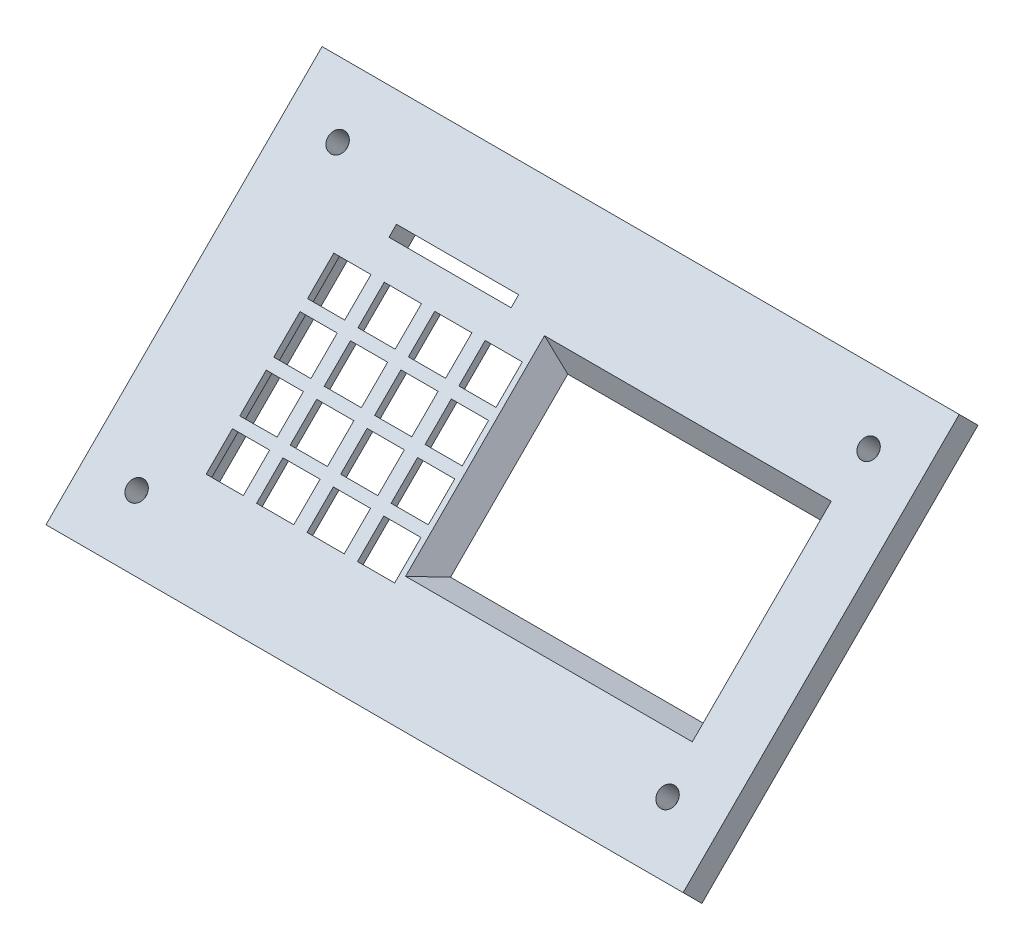
SolidWorks part; units mm, degrees
ref_plane "Спереди" through (0, 0, 0) normal (0, 0, 1) x (1, 0, 0)
ref_plane "Сверху" through (0, 0, 0) normal (0, 1, 0) x (1, 0, 0)
ref_plane "Справа" through (0, 0, 0) normal (1, 0, 0) x (0, 0, -1)
ref_plane "Плоскость4" through (0, 0, 0) normal (0, 0.7071, 0.7071) x (1, 0, 0)
sketch "Эскиз1" plane through (0, 0, 0) normal (0, 0.7071, 0.7071) x (1, 0, 0)
  line L0 (58, 52) -> (106, 52)
  line L1 (120, 0) -> (120, 73.5391)
  line L2 (106, 52) -> (106, 21)
  line L3 (106, 21) -> (58, 21)
  line L4 (58, 21) -> (58, 52)
  line L5 (48, 58) -> (48, 56)
  line L6 (120, -28.6) -> (120, 28.6) construction
  line L7 (120, 73.5391) -> (0, 73.5391) construction
  line L8 (0, 73.5391) -> (0, 0)
  line L9 (48, 58) -> (25, 58)
  line L10 (25, 58) -> (25, 56)
  line L11 (0, 28.6) -> (0, -28.6) construction
  line L12 (0, 0) -> (120, 0)
  line L13 (0, 73.5391) -> (120, 73.5391)
  line L14 (54, 50.5) -> (47, 50.5)
  line L15 (25, 56) -> (48, 56)
  line L16 (44.5, 50.5) -> (37.5, 50.5)
  line L18 (35, 50.5) -> (28, 50.5)
  line L20 (25.5, 50.5) -> (18.5, 50.5)
  line L21 (18.5, 50.5) -> (18.5, 43.5)
  line L22 (18.5, 43.5) -> (25.5, 43.5)
  line L23 (25.5, 43.5) -> (25.5, 50.5)
  line L24 (18.5, 41.5) -> (25.5, 41.5)
  line L25 (25.5, 41.5) -> (25.5, 34.5)
  line L26 (25.5, 34.5) -> (18.5, 34.5)
  line L27 (18.5, 34.5) -> (18.5, 41.5)
  line L28 (18.5, 32.5) -> (18.5, 25.4558)
  line L29 (0, 25.4558) -> (120, 25.4558) construction
  line L30 (18.5, 25.4558) -> (25.5, 25.5)
  line L31 (25.5, 25.5) -> (25.5, 32.5)
  line L32 (25.5, 32.5) -> (18.5, 32.5)
  line L33 (18.5, 23.5) -> (18.5, 16.5)
  line L34 (18.5, 16.5) -> (25.5, 16.5)
  line L35 (25.5, 16.5) -> (25.5, 23.5)
  line L36 (25.5, 23.5) -> (18.5, 23.5)
  line L37 (28, 16.5) -> (28, 23.5)
  line L38 (28, 23.5) -> (35, 23.5)
  line L39 (35, 23.5) -> (35, 16.5)
  line L40 (35, 16.5) -> (28, 16.5)
  line L41 (37.5, 23.5) -> (37.5, 16.5)
  line L42 (37.5, 16.5) -> (44.5, 16.5)
  line L43 (44.5, 16.5) -> (44.5, 23.5)
  line L44 (44.5, 23.5) -> (37.5, 23.5)
  line L45 (47, 16.5) -> (47, 23.5)
  line L46 (47, 23.5) -> (54, 23.5)
  line L47 (54, 23.5) -> (54, 16.5)
  line L48 (54, 16.5) -> (47, 16.5)
  line L49 (54, 25.4558) -> (54, 32.5)
  line L50 (54, 32.5) -> (47, 32.5)
  line L51 (47, 32.5) -> (47, 25.4558)
  line L52 (47, 25.4558) -> (54, 25.4558)
  line L53 (44.5, 34.5) -> (44.5, 41.5)
  line L54 (44.5, 41.5) -> (37.5, 41.5)
  line L55 (37.5, 41.5) -> (37.5, 34.5)
  line L56 (37.5, 34.5) -> (44.5, 34.5)
  line L57 (35, 43.5) -> (28, 43.5)
  line L58 (28, 43.5) -> (28, 50.5)
  line L59 (35, 43.5) -> (35, 50.5)
  line L60 (37.5, 43.5) -> (37.5, 50.5)
  line L61 (44.5, 50.5) -> (44.5, 43.5)
  line L62 (44.5, 43.5) -> (37.5, 43.5)
  line L63 (54, 50.5) -> (54, 43.5)
  line L64 (47, 43.5) -> (47, 50.5)
  line L65 (54, 43.5) -> (47, 43.5)
  line L66 (47, 41.5) -> (47, 34.5)
  line L67 (47, 34.5) -> (54, 34.5)
  line L68 (54, 34.5) -> (54, 41.5)
  line L69 (54, 41.5) -> (47, 41.5)
  line L70 (28, 41.5) -> (35, 41.5)
  line L71 (35, 41.5) -> (35, 34.5)
  line L72 (35, 34.5) -> (28, 34.5)
  line L73 (28, 34.5) -> (28, 41.5)
  line L74 (28, 32.5) -> (28, 25.4558)
  line L75 (28, 25.4558) -> (35, 25.4558)
  line L76 (35, 25.4558) -> (35, 32.5)
  line L77 (35, 32.5) -> (28, 32.5)
  line L78 (37.5, 32.5) -> (37.5, 25.4558)
  line L79 (37.5, 25.4558) -> (44.5, 25.4558)
  line L80 (44.5, 25.4558) -> (44.5, 32.5)
  line L81 (44.5, 32.5) -> (37.5, 32.5)
  circle A0 centre (10, 63.5391) radius 1.8
  circle A1 centre (110, 63.5391) radius 1.8
  circle A2 centre (110, 10) radius 1.8
  circle A3 centre (10, 10) radius 1.8
extrude "Бобышка-Вытянуть1" add sketch "Эскиз1" along normal blind 5
chamfer "Фаска1" distance 3 angle 60 4 edges at (58, 29.3449, -22.2739) (82, 18.3848, -11.3137) (106, 29.3449, -22.2739) (82, 40.3051, -33.234) first distance on face at (110, 9.3338, -2.2627)
sketch "Эскиз2" plane through (0, 0, 0) normal (0, 0.7071, 0.7071) x (1, 0, 0)
  line L0 (17.5, 15.5428) -> (17.5, 51.6529)
  line L1 (17.5, 51.6529) -> (55, 51.6529)
  line L4 (17.5, 15.5428) -> (55, 15.5428)
  line L5 (55, 15) -> (55, 58) construction
  line L6 (55, 15.5428) -> (55, 51.6529)
extrude "Вырез-Вытянуть1" cut sketch "Эскиз2" along normal blind 3.5
